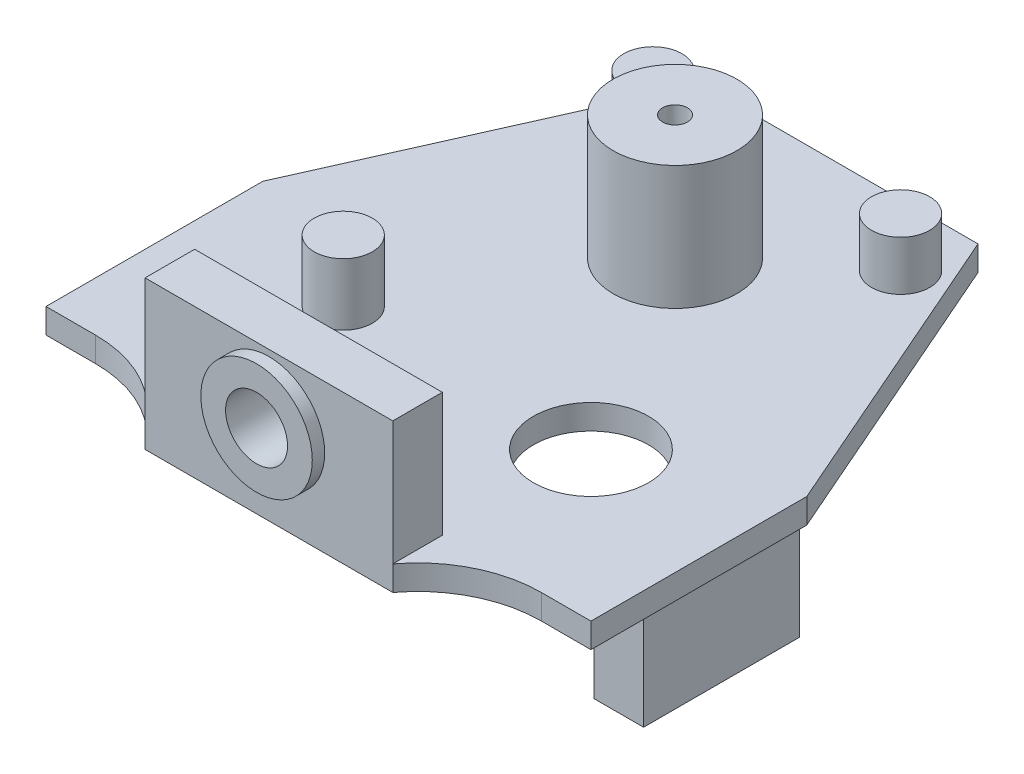
SolidWorks part; units mm, degrees
ref_plane "Front Plane" through (0, 0, 0) normal (0, 0, 1) x (1, 0, 0)
ref_plane "Top Plane" through (0, 0, 0) normal (0, 1, 0) x (1, 0, 0)
ref_plane "Right Plane" through (0, 0, 0) normal (1, 0, 0) x (0, 0, -1)
sketch "Sketch1" plane through (0, 0, 0) normal (0, 1, 0) x (1, 0, 0)
  line L1 (-20, 10) -> (20, 10)
  line L2 (-20, 10) -> (-20, -10)
  line L3 (-20, -10) -> (20, -10)
  line L4 (20, 10) -> (20, -10)
  point P4 (0, 10)
  point P6 (20, 0)
  dimension "D1" = 40
  dimension "D2" = 20
extrude "Boss-Extrude1" add sketch "Sketch1" along normal blind 2
sketch "Sketch2" plane through (0, 2, 0) normal (0, 1, 0) x (1, 0, 0)
  line L0 (-20, 0) -> (-4, 0) construction
  line L1 (-20, 10) -> (-20, -10) construction
  circle A0 centre (-4, 0) radius 2.35
  dimension "D2" = 4.7
  dimension "D1" = 16
sketch "Sketch5" plane through (0, 2, 0) normal (0, 1, 0) x (1, 0, 0)
  line L1 (-20, 10) -> (30, 10)
  line L2 (-20, 10) -> (-20, 30)
  line L3 (-20, 30) -> (30, 30)
  line L4 (30, 10) -> (30, 30)
  dimension "D1" = 20
extrude "Boss-Extrude4" add sketch "Sketch5" against normal blind 2
sketch "Sketch6" plane through (0, 2, 0) normal (0, 1, 0) x (1, 0, 0)
  line L0 (-20, 25) -> (20, 25) construction
  line L1 (-20, 30) -> (-20, -10) construction
  line L2 (20, -10) -> (20, 10) construction
  line L3 (30, 30) -> (-20, 30) construction
  line L4 (0, 30) -> (0, 25) construction
  circle A0 centre (-10, 25) radius 2.35
  circle A1 centre (10, 25) radius 2.35
  dimension "D2" = 4.7
  dimension "D3" = 4.7
  dimension "D4" = 20
  dimension "D1" = 5
  dimension "D5" = 10
extrude "Boss-Extrude5" add sketch "Sketch6" along normal blind 4
sketch "Sketch7" plane through (0, 0, 0) normal (0, -1, 0) x (1, 0, 0)
  line L1 (-11.55, -6.3) -> (-7, -6.3)
  line L2 (-11.55, -6.3) -> (-11.55, 6.3)
  line L3 (-11.55, 6.3) -> (-7, 6.3)
  line L4 (-7, -6.3) -> (-7, 6.3)
  line L5 (16, 6.3) -> (20.55, 6.3)
  line L6 (16, 6.3) -> (16, -6.2998)
  line L7 (16, -6.2998) -> (20.55, -6.2998)
  line L8 (20.55, 6.3) -> (20.55, -6.2998)
sketch "Sketch15" plane through (0, 2, 0) normal (0, 1, 0) x (1, 0, 0)
  line L0 (-20, 0) -> (17.0642, 0) construction
  line L1 (-20, 30) -> (-20, -10) construction
  line L2 (-20, -10) -> (20, -10) construction
  line L4 (0, -10) -> (0, 30) construction
  line L5 (30, 30) -> (-20, 30) construction
  circle A0 centre (10, 0) radius 4.65
  dimension "D2" = 9.3
  dimension "D1" = 10
extrude "Cut-Extrude6" cut sketch "Sketch15" against normal blind 6
sketch "Sketch17" plane through (0, 2, 0) normal (0, 1, 0) x (1, 0, 0)
  line L1 (20, 10) -> (30, 10)
  line L2 (20, 10) -> (20, 30)
  line L3 (20, 30) -> (30, 30)
  line L4 (30, 10) -> (30, 30)
extrude "Cut-Extrude8" cut sketch "Sketch17" against normal through all
sketch "Sketch18" plane through (0, 2, 0) normal (0, 1, 0) x (1, 0, 0)
  line L0 (20, 10) -> (-20, 10) construction
  line L1 (20, -10) -> (20, 30) construction
  line L2 (-20, 30) -> (-20, -10) construction
  line L3 (11.25, 30) -> (-11.1, 30) construction
  line L4 (20, 30) -> (-20, 30) construction
  line L5 (-11.1, 30) -> (-20, 10) construction
  line L6 (11.25, 30) -> (20, 10) construction
  line L7 (-11.1, 30) -> (-20, 10)
  line L8 (-20, 10) -> (-20, 30)
  line L9 (-20, 30) -> (-11.1, 30)
  line L10 (20, 10) -> (11.25, 30)
  line L11 (11.25, 30) -> (20, 30)
  line L12 (20, 30) -> (20, 10)
extrude "Cut-Extrude9" cut sketch "Sketch18" against normal blind 2
sketch "Sketch19" plane through (0, 2, 0) normal (0, 1, 0) x (1, 0, 0)
  circle A0 centre (-10, 0) radius 2.35
  dimension "D2" = 4.7
extrude "Boss-Extrude6" add sketch "Sketch19" along normal blind 5
sketch "Sketch20" plane through (0, 2, 0) normal (0, 1, 0) x (1, 0, 0)
  line L0 (-20, 10) -> (-22, 5.5056)
  line L1 (20, -10) -> (-20, -10)
  line L3 (20, -12) -> (-20, -12)
  line L6 (-20, 10) -> (-20, -10)
  line L7 (-20, -12) -> (-22, -12)
  line L8 (-22, 5.5056) -> (-22, -12)
  line L10 (20, 10) -> (20, -10)
  line L11 (20, -12) -> (22, -12)
  line L12 (22, 5.4286) -> (22, -12)
  line L13 (20, 10) -> (22, 5.4286)
  line L14 (-20, 10) -> (-11.1, 30) construction
  dimension "D1" = 2
  dimension "D3" = 2
  dimension "D4" = 180
  dimension "D5" = 2
extrude "Boss-Extrude7" add sketch "Sketch20" against normal blind 2
sketch "Sketch21" plane through (0, 2, 0) normal (0, 1, 0) x (1, 0, 0)
  circle A0 centre (0, 16.7878) radius 5
  dimension "D1" = 10
extrude "Boss-Extrude8" add sketch "Sketch21" along normal blind 10
sketch "Sketch22" plane through (0, 12, 0) normal (0, 1, 0) x (1, 0, 0)
  circle A0 centre (0, 16.7878) radius 1
  dimension "D1" = 2
extrude "Cut-Extrude10" cut sketch "Sketch22" against normal blind 8 draft 1
sketch "Sketch23" plane through (0, 0, 0) normal (0, -1, 0) x (1, 0, 0)
  line L0 (-7, -6.3) -> (-11.55, -6.3) construction
  line L1 (-11.55, 6.3) -> (-7.55, 6.3)
  line L2 (-11.55, 6.3) -> (-11.55, -6.3)
  line L3 (-11.55, -6.3) -> (-7.55, -6.3)
  line L4 (-7.55, 6.3) -> (-7.55, -6.3)
  line L5 (20.55, -6.2998) -> (16, -6.3) construction
  line L6 (20.55, 6.3002) -> (16.55, 6.3002)
  line L7 (20.55, 6.3002) -> (20.55, -6.3)
  line L8 (20.55, -6.3) -> (16.55, -6.3)
  line L9 (16.55, 6.3002) -> (16.55, -6.3)
  dimension "D1" = 4
  dimension "D2" = 4
extrude "Boss-Extrude9" add sketch "Sketch23" along normal blind 9
sketch "Sketch24" plane through (0, -9, 0) normal (0, -1, 0) x (1, 0, 0)
  circle A0 centre (18.2671, 0.0151) radius 1
  circle A1 centre (-9.275, 0) radius 1
  dimension "D1" = 2
  dimension "D2" = 2
extrude "Cut-Extrude11" cut sketch "Sketch24" against normal blind 6 draft 1
sketch "Sketch25" plane through (0, 0, 12) normal (0, 0, 1) x (1, 0, 0)
  line L0 (-22, 2) -> (22, 2) construction
  line L1 (-10, 2) -> (10, 2)
  line L2 (-10, 2) -> (-10, 0)
  line L3 (-10, 0) -> (10, 0)
  line L4 (10, 2) -> (10, 0)
  line L5 (-22, 0) -> (22, 0) construction
  point P8 (0, 2)
  dimension "D1" = 20
extrude "Boss-Extrude10" add sketch "Sketch25" along normal blind 4
sketch "Sketch26" plane through (0, 2, 0) normal (0, 1, 0) x (1, 0, 0)
  line L0 (10, -16) -> (10, -12) construction
  line L1 (-10, -16) -> (10, -16)
  line L2 (-10, -16) -> (-10, -12)
  line L3 (-10, -12) -> (10, -12)
  line L4 (10, -16) -> (10, -12)
  dimension "D1" = 4
extrude "Boss-Extrude11" add sketch "Sketch26" along normal blind 10
fillet "Fillet1" radius 10 2 edges at (10, 1, 12) (-10, 1, 12)
sketch "Sketch27" plane through (0, 0, 12) normal (0, 0, -1) x (-1, 0, 0)
  line L0 (-10, 7) -> (10, 7) construction
  line L1 (-10, 12) -> (-10, 2) construction
  line L2 (12.35, 7) -> (7.65, 7) construction
  line L3 (0, 12) -> (-0.075, 2) construction
  line L4 (5, 12) -> (-5, 12) construction
  line L5 (-11.25, 2) -> (11.1, 2) construction
  circle A0 centre (0, 7) radius 1
  dimension "D1" = 2
extrude "Cut-Extrude13" cut sketch "Sketch27" against normal through all
sketch "Sketch28" plane through (0, 0, 16) normal (0, 0, 1) x (1, 0, 0)
  circle A0 centre (0, 7) radius 2.5
  dimension "D1" = 5
extrude "Cut-Extrude14" cut sketch "Sketch28" against normal blind 3
sketch "Sketch29" plane through (0, 0, 16) normal (0, 0, 1) x (1, 0, 0)
  circle A0 centre (0, 7) radius 2.5
  circle A1 centre (0, 7) radius 4.5
  dimension "D1" = 2
extrude "Boss-Extrude12" add sketch "Sketch29" along normal blind 1
sketch "Sketch30" plane through (0, 0, 12) normal (0, 0, -1) x (-1, 0, 0)
  circle A0 centre (0, 7) radius 1
  circle A1 centre (0, 7) radius 2
  dimension "D1" = 2
  dimension "D2" = 1
